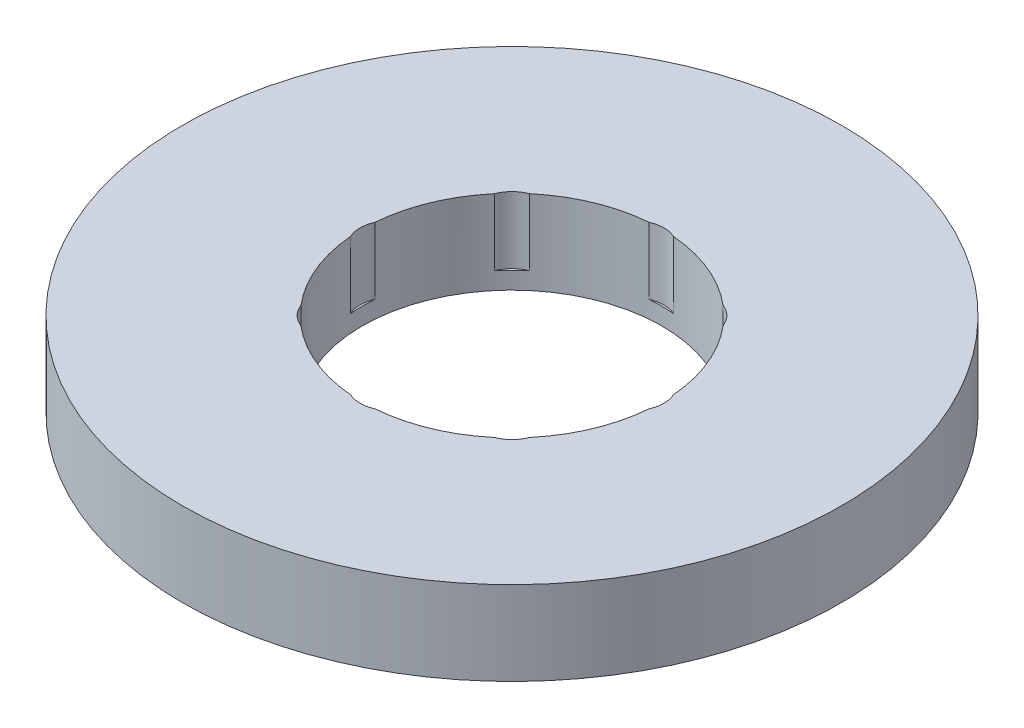
SolidWorks part; units mm, degrees
ref_plane "Front Plane" through (0, 0, 0) normal (0, 0, 1) x (1, 0, 0)
ref_plane "Top Plane" through (0, 0, 0) normal (0, 1, 0) x (1, 0, 0)
ref_plane "Right Plane" through (0, 0, 0) normal (1, 0, 0) x (0, 0, -1)
sketch "Sketch1" plane through (0, 0, 0) normal (0, 1, 0) x (1, 0, 0)
  circle A0 centre (0, 0) radius 82.5
  dimension "FLANGE_OD" = 165
extrude "Boss-Extrude1" add sketch "Sketch1" along normal blind 21
sketch "Sketch2" plane through (0, 0, 0) normal (0, 1, 0) x (1, 0, 0)
  circle A0 centre (0, 0) radius 37.5
  dimension "BORE_D" = 75
extrude "Cut-Extrude1" cut sketch "Sketch2" along normal through all
sketch "Sketch3" plane through (0, 21, 0) normal (0, 1, 0) x (1, 0, 0)
  circle A0 centre (0, 0) radius 30.5324 construction
  circle A1 centre (-30.5324, 0) radius 7.4986
  dimension "BOLT_D" = 14.9972
  dimension "BOLT_PCD" = 61.0647
extrude "Cut-Extrude2" cut sketch "Sketch3" against normal blind 16.7079
pattern_circular "CirPattern1" count 8 over 360 about axis through (0, 0, 0) along (0, 1, 0) of "Cut-Extrude2"
